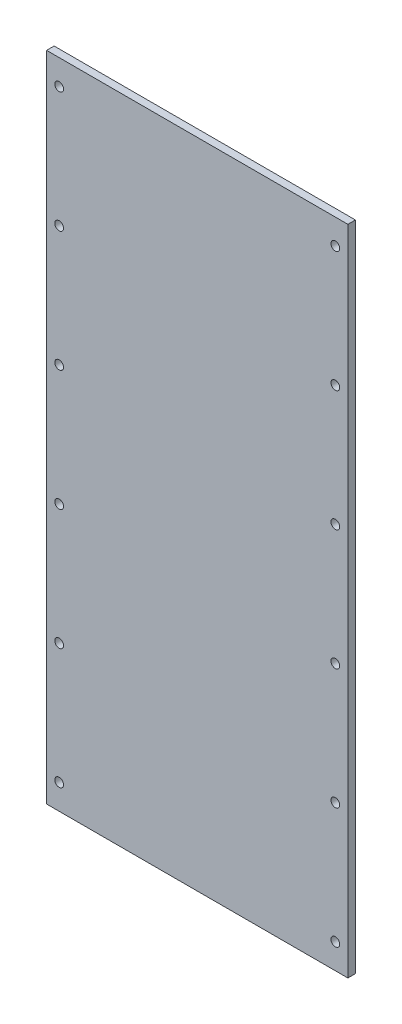
SolidWorks part; units mm, degrees
ref_plane "Plan de face" through (0, 0, 0) normal (0, 0, 1) x (1, 0, 0)
ref_plane "Plan de dessus" through (0, 0, 0) normal (0, 1, 0) x (1, 0, 0)
ref_plane "Plan de droite" through (0, 0, 0) normal (1, 0, 0) x (0, 0, -1)
sketch "Esquisse1" plane through (0, 0, 0) normal (0, 0, 1) x (1, 0, 0)
  line L1 (60, -130) -> (-60, -130)
  line L2 (60, -130) -> (60, 130)
  line L3 (60, 130) -> (-60, 130)
  line L4 (-60, -130) -> (-60, 130)
  line L5 (60, -130) -> (-60, 130) construction
  line L6 (60, 130) -> (-60, -130) construction
  point P0 (0, 0)
  dimension "D1" = 260
  dimension "D2" = 120
extrude "Boss.-Extru.1" add sketch "Esquisse1" along normal blind 3
sketch "Esquisse2" plane through (0, 0, 3) normal (0, 0, 1) x (1, 0, 0)
  line L0 (60, 130) -> (-60, 130) construction
  line L2 (-55, 120) -> (60, 120) construction
  line L3 (60, -130) -> (60, 130) construction
  line L4 (-55, 120) -> (-55, -130) construction
  line L5 (-60, -130) -> (60, -130) construction
  line L7 (0, 0) -> (0, -130) construction
  line L15 (55, 120) -> (55, -130) construction
  circle A0 centre (-55, 120) radius 1.7476
  circle A2 centre (55, 120) radius 1.7476
  circle A3 centre (-55, 72) radius 1.7476
  circle A4 centre (-55, 24) radius 1.7476
  circle A5 centre (-55, -24) radius 1.7476
  circle A6 centre (-55, -72) radius 1.7476
  circle A11 centre (55, 72) radius 1.7476
  circle A12 centre (55, 24) radius 1.7476
  circle A13 centre (55, -24) radius 1.7476
  circle A14 centre (55, -72) radius 1.7476
  circle A24 centre (55, -120) radius 1.7476
  circle A25 centre (0, 120) radius 1.7476 [skipped]
  circle A26 centre (-55, -120) radius 1.7476
  dimension "D1" = 10
  dimension "D2" = 10
  dimension "D4" = 5
  dimension "D6" = 10
  dimension "D3" = 3
  dimension "D5" = 6
extrude "Enlèv. mat.-Extru.1" cut sketch "Esquisse2" against normal blind 10
